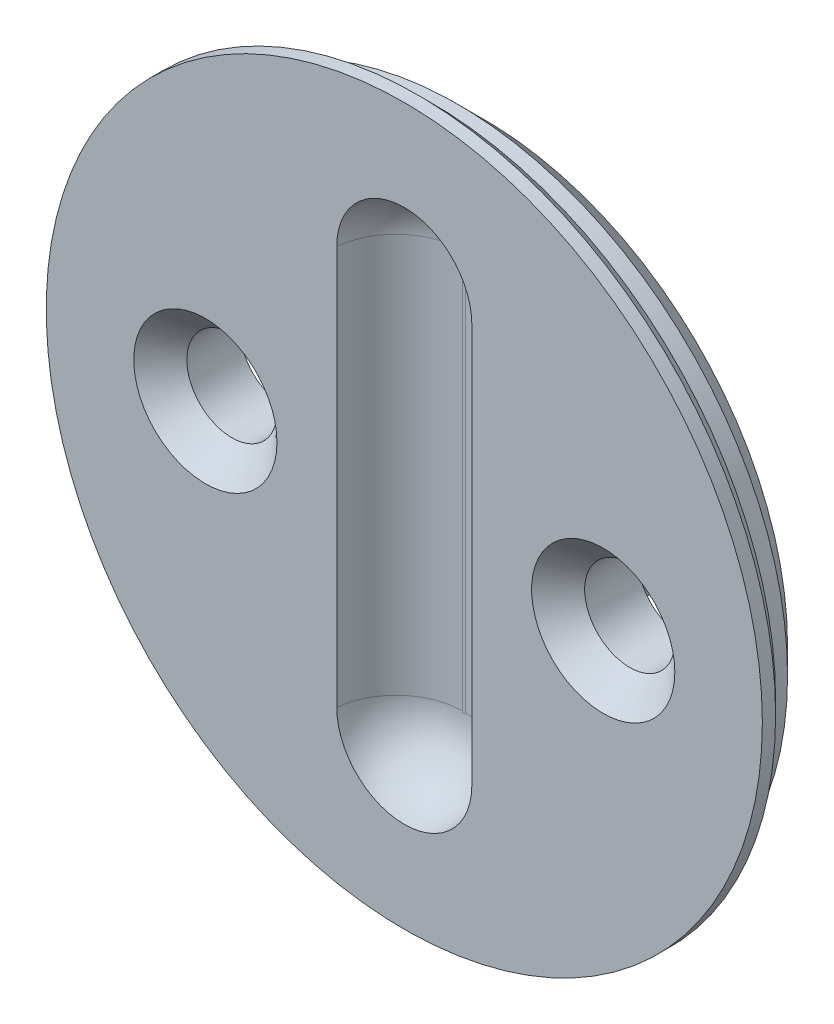
SolidWorks part; units mm, degrees
ref_plane "Front Plane" through (0, 0, 0) normal (0, 0, 1) x (1, 0, 0)
ref_plane "Top Plane" through (0, 0, 0) normal (0, 1, 0) x (1, 0, 0)
ref_plane "Right Plane" through (0, 0, 0) normal (1, 0, 0) x (0, 0, -1)
sketch "Sketch1" plane through (0, 0, 0) normal (0, 0, 1) x (1, 0, 0)
  line L0 (0, 9.3188) -> (0, -6.9028) construction
  circle A0 centre (0, 0) radius 12.45
  circle A1 centre (-7.5, 0) radius 1.7
  circle A2 centre (7.5, 0) radius 1.7
  dimension "D2" = 24.9
  dimension "D3" = 3.4
  dimension "D1" = 15
extrude "Boss-Extrude1" add sketch "Sketch1" against normal blind 2
sketch "Sketch2" plane through (0, 0, -2) normal (0, 0, -1) x (-1, 0, 0)
  line L1 (-3.85, 3.35) -> (3.85, 3.35)
  line L2 (-3.85, 3.35) -> (-3.85, -3.35)
  line L3 (-3.85, -3.35) -> (3.85, -3.35)
  line L4 (3.85, 3.35) -> (3.85, -3.35)
  line L5 (-3.85, 3.35) -> (3.85, -3.35) construction
  line L6 (-3.85, -3.35) -> (3.85, 3.35) construction
  point P0 (0, 0)
  dimension "D1" = 6.7
  dimension "D2" = 7.7
extrude "Boss-Extrude2" add sketch "Sketch2" along normal blind 3.5
sketch "Sketch3" plane through (0, 0, 0) normal (0, 0, 1) x (1, 0, 0)
  circle A0 centre (0, 0) radius 13.5
  circle A1 centre (-7.5, 0) radius 1.7
  circle A2 centre (7.5, 0) radius 1.7
  circle A3 centre (-7.5, 0) radius 1.7 construction
  dimension "D1" = 27
extrude "Boss-Extrude3" add sketch "Sketch3" along normal blind 1
chamfer "Chamfer1" distance 1 angle 45 5 edges at (0, 3.35, -5.5) (3.85, 0, -5.5) (0, -3.35, -5.5) (-3.85, 0, -5.5) (12.45, 0, -2)
chamfer "Chamfer2" distance 0.5 angle 45 1 edges at (13.5, 0, 0)
sketch "Sketch4" plane through (0, 0, 1) normal (0, 0, 1) x (1, 0, 0)
  line L0 (0, 7.5257) -> (0, -7.5257) construction
  line L1 (2.5463, 7.5257) -> (2.5463, -7.5257)
  line L2 (-2.5463, 7.5257) -> (-2.5463, -7.5257)
  arc A0 (2.5463, 7.5257) -> (-2.5463, 7.5257) centre (0, 7.5257) ccw
  arc A1 (-2.5463, -7.5257) -> (2.5463, -7.5257) centre (0, -7.5257) ccw
  point P2 (0, 0)
extrude "Cut-Extrude1" cut sketch "Sketch4" against normal blind 2.25
fillet "Fillet1" radius 2.5 4 edges at (-2.5463, 0, -1.25) (2.5463, 0, -1.25) (0, 10.0719, -1.25) (0, -10.0719, -1.25)
chamfer "Chamfer3" distance 1 angle 45 2 edges at (9.2, 0, 1) (-5.8, 0, 1)
